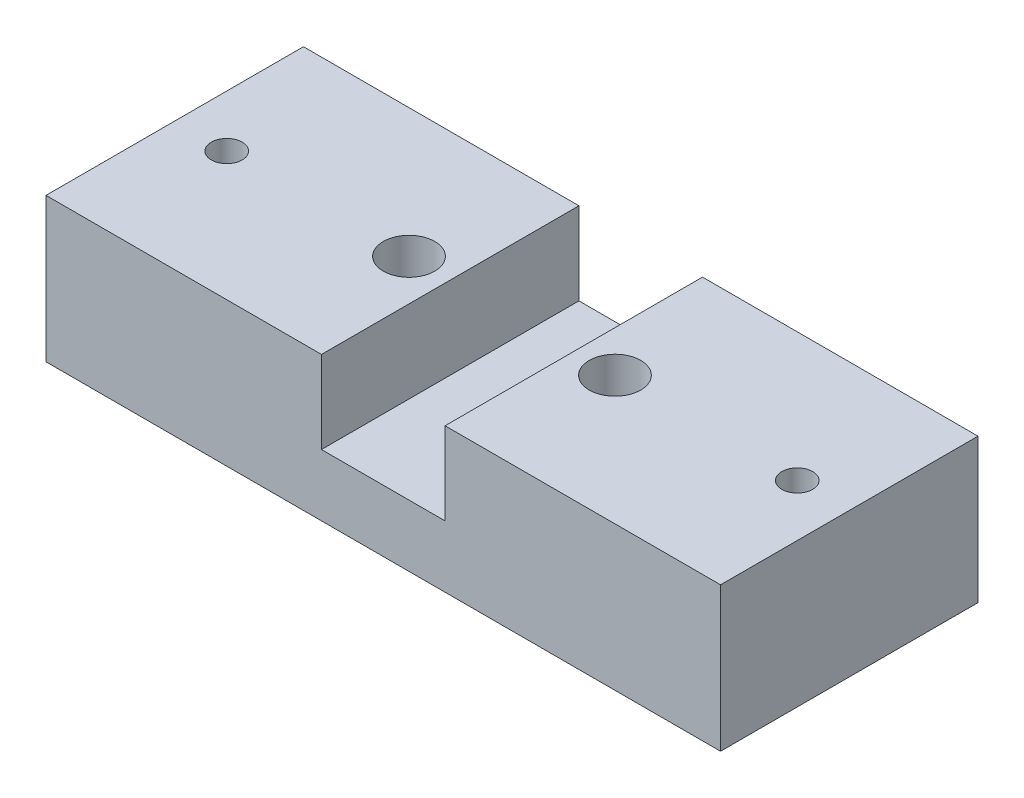
SolidWorks part; units mm, degrees
ref_plane "Płaszczyzna przednia" through (0, 0, 0) normal (0, 0, 1) x (1, 0, 0)
ref_plane "Płaszczyzna górna" through (0, 0, 0) normal (0, 1, 0) x (1, 0, 0)
ref_plane "Płaszczyzna prawa" through (0, 0, 0) normal (1, 0, 0) x (0, 0, -1)
sketch "Sketch1" plane through (0, 0, 0) normal (0, 0, 1) x (1, 0, 0)
  line L0 (26.75, 14) -> (26.75, 6)
  line L1 (0, 0) -> (65.5, 0)
  line L2 (0, 0) -> (0, 14)
  line L3 (0, 14) -> (26.75, 14)
  line L4 (65.5, 0) -> (65.5, 14)
  line L5 (26.75, 6) -> (38.75, 6)
  line L6 (38.75, 6) -> (38.75, 14)
  line L7 (38.75, 14) -> (65.5, 14)
  dimension "D1" = 65.5
  dimension "D2" = 14
  dimension "D3" = 26.75
  dimension "D4" = 26.75
  dimension "D5" = 8
extrude "Boss-Extrude1" add sketch "Sketch1" along normal blind 25
hole_wizard "Ø3.0mm Dowel Hole1" positions "Sketch2" profile "Sketch4" hole size "Ø3.0" standard "ANSI Metric" end condition through all
sketch "Sketch2" plane through (0, 14, 0) normal (0, 1, 0) x (1, 0, 0)
  line L2 (65.5, -25) -> (38.75, -25) construction
  line L3 (65.5, -25) -> (65.5, 0) construction
  line L4 (0, -25) -> (0, 0) construction
  point P0 (5.05, -12.5)
  point P2 (60.45, -12.5)
  dimension "D1" = 5.05
  dimension "D2" = 5.05
  dimension "D3" = 12.5
sketch "Sketch4" plane through (5.05, 14, 12.5) normal (1, 0, 0) x (0, 0, 1)
  line L0 (0, 0) -> (0, 14)
  line L1 (0, 14) -> (1.5, 14)
  line L2 (1.5, 14) -> (1.5, 0)
  line L5 (1.5, 0) -> (0, 0)
  line L11 (0, -6.35) -> (0, 107.95) construction
  dimension "Thru Hole Dia." = 3
  dimension "Thru Hole Depth" = 14
sketch "Sketch5" plane through (0, 0, 0) normal (0, 1, 0) x (1, 0, 0)
  line L0 (65.5, -25) -> (38.75, -25) construction
  line L1 (0, -25) -> (0, 0) construction
  circle A0 centre (50.65, -13) radius 5
  circle A1 centre (14.45, -13) radius 5
  dimension "D1" = 10
  dimension "D2" = 10
  dimension "D4" = 36.2
  dimension "D5" = 14.45
  dimension "D3" = 12
extrude "Cut-Extrude1" cut sketch "Sketch5" along normal blind 4
hole_wizard "Ø5.0mm Dowel Hole1" positions "Sketch6" profile "Sketch7" hole size "Ø5.0" standard "ANSI Metric" end condition through all
sketch "Sketch6" plane through (0, 14, 0) normal (0, 1, 0) x (1, 0, 0)
  line L0 (65.5, -25) -> (38.75, -25) construction
  line L1 (0, -25) -> (0, 0) construction
  point P0 (42.75, -12.5)
  point P2 (22.75, -12.5)
  dimension "D1" = 12.5
  dimension "D2" = 20
  dimension "D3" = 22.75
sketch "Sketch7" plane through (42.75, 14, 12.5) normal (1, 0, 0) x (0, 0, 1)
  line L0 (0, 0) -> (0, 14)
  line L1 (0, 14) -> (2.5, 14)
  line L2 (2.5, 14) -> (2.5, 0)
  line L5 (2.5, 0) -> (0, 0)
  line L11 (0, -6.35) -> (0, 107.95) construction
  dimension "Thru Hole Dia." = 5
  dimension "Thru Hole Depth" = 14
